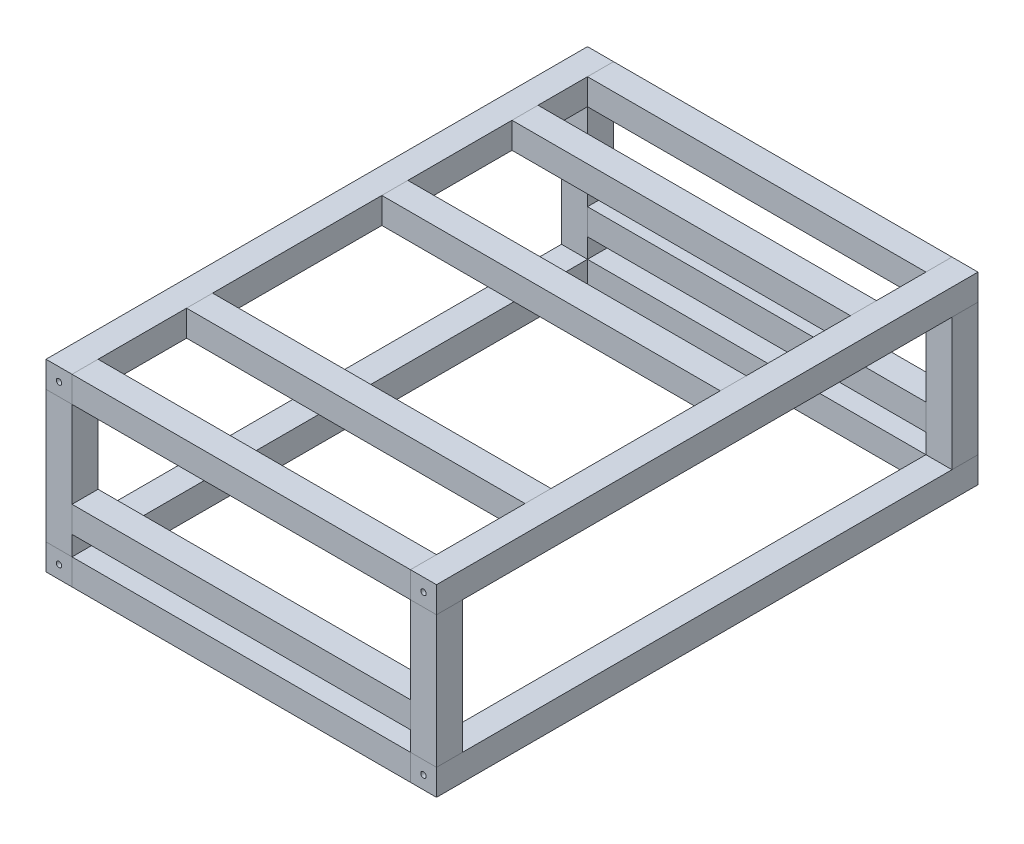
SolidWorks part; units mm, degrees
ref_plane "Front Plane" through (0, 0, 0) normal (0, 0, 1) x (1, 0, 0)
ref_plane "Top Plane" through (0, 0, 0) normal (0, 1, 0) x (1, 0, 0)
ref_plane "Right Plane" through (0, 0, 0) normal (1, 0, 0) x (0, 0, -1)
ref_plane "PL_Xm208" through (0, 0, -208) normal (0, 0, 1) x (1, 0, 0)
sketch "SK_BotSideRails" plane through (0, 0, -208) normal (0, 0, 1) x (1, 0, 0)
  line L1 (130, 36.5) -> (150, 36.5)
  line L2 (130, 36.5) -> (130, 56.5)
  line L3 (130, 56.5) -> (150, 56.5)
  line L4 (150, 36.5) -> (150, 56.5)
  line L6 (-130, 36.5) -> (-150, 36.5)
  line L7 (-130, 36.5) -> (-130, 56.5)
  line L8 (-130, 56.5) -> (-150, 56.5)
  line L9 (-150, 36.5) -> (-150, 56.5)
  circle A0 centre (140, 46.5) radius 2.1
  circle A1 centre (-140, 46.5) radius 2.1
  dimension "D7" = 4.2
  dimension "D14" = 4.2
  dimension "D1" = 20
  dimension "D2" = 20
  dimension "D3" = 130
  dimension "D4" = 36.5
  dimension "D5" = 140
  dimension "D6" = 46.5
  dimension "D8" = 20
  dimension "D9" = 20
  dimension "D10" = 130
  dimension "D11" = 36.5
  dimension "D12" = 140
  dimension "D13" = 46.5
extrude "EX_BotSideRails" add sketch "SK_BotSideRails" along normal blind 416 separate body
sketch "SK_TopSideRails" plane through (0, 0, -208) normal (0, 0, 1) x (1, 0, 0)
  line L1 (130, 158) -> (150, 158)
  line L2 (130, 158) -> (130, 178)
  line L3 (130, 178) -> (150, 178)
  line L4 (150, 158) -> (150, 178)
  line L6 (-130, 158) -> (-150, 158)
  line L7 (-130, 158) -> (-130, 178)
  line L8 (-130, 178) -> (-150, 178)
  line L9 (-150, 158) -> (-150, 178)
  circle A0 centre (140, 168) radius 2.1
  circle A1 centre (-140, 168) radius 2.1
  dimension "D7" = 4.2
  dimension "D14" = 4.2
  dimension "D1" = 20
  dimension "D2" = 20
  dimension "D3" = 130
  dimension "D5" = 140
  dimension "D8" = 20
  dimension "D9" = 20
  dimension "D10" = 130
  dimension "D12" = 140
  dimension "D4" = 158
  dimension "D6" = 168
  dimension "D11" = 158
  dimension "D13" = 168
extrude "EX_TopSideRails" add sketch "SK_TopSideRails" along normal blind 416 separate body
ref_plane "PL_Ym130" through (-130, 0, 0) normal (1, 0, 0) x (0, 0, -1)
sketch "SK_BotEndRails" plane through (-130, 0, 0) normal (1, 0, 0) x (0, 0, -1)
  line L1 (-188, 36.5) -> (-208, 36.5)
  line L2 (-188, 36.5) -> (-188, 56.5)
  line L3 (-188, 56.5) -> (-208, 56.5)
  line L4 (-208, 36.5) -> (-208, 56.5)
  line L6 (188, 36.5) -> (208, 36.5)
  line L7 (188, 36.5) -> (188, 56.5)
  line L8 (188, 56.5) -> (208, 56.5)
  line L9 (208, 36.5) -> (208, 56.5)
  circle A0 centre (-198, 46.5) radius 2.1
  circle A1 centre (198, 46.5) radius 2.1
  dimension "D7" = 4.2
  dimension "D14" = 4.2
  dimension "D1" = 20
  dimension "D2" = 20
  dimension "D4" = 36.5
  dimension "D6" = 46.5
  dimension "D8" = 20
  dimension "D9" = 20
  dimension "D11" = 36.5
  dimension "D13" = 46.5
  dimension "D3" = 188
  dimension "D5" = 198
  dimension "D10" = 188
  dimension "D12" = 198
extrude "EX_BotEndRails" add sketch "SK_BotEndRails" along normal blind 260 separate body
sketch "SK_TopEndRails" plane through (-130, 0, 0) normal (1, 0, 0) x (0, 0, -1)
  line L1 (-188, 158) -> (-208, 158)
  line L2 (-188, 158) -> (-188, 178)
  line L3 (-188, 178) -> (-208, 178)
  line L4 (-208, 158) -> (-208, 178)
  line L6 (188, 158) -> (208, 158)
  line L7 (188, 158) -> (188, 178)
  line L8 (188, 178) -> (208, 178)
  line L9 (208, 158) -> (208, 178)
  circle A0 centre (-198, 168) radius 2.1
  circle A1 centre (198, 168) radius 2.1
  dimension "D7" = 4.2
  dimension "D14" = 4.2
  dimension "D1" = 20
  dimension "D2" = 20
  dimension "D8" = 20
  dimension "D9" = 20
  dimension "D4" = 158
  dimension "D6" = 168
  dimension "D11" = 158
  dimension "D13" = 168
  dimension "D3" = 188
  dimension "D5" = 198
  dimension "D10" = 188
  dimension "D12" = 198
extrude "EX_TopEndRails" add sketch "SK_TopEndRails" along normal blind 260 separate body
sketch "SK_MidCross" plane through (-130, 0, 0) normal (1, 0, 0) x (0, 0, -1)
  line L1 (-188, 71.5) -> (-208, 71.5)
  line L2 (-188, 71.5) -> (-188, 91.5)
  line L3 (-188, 91.5) -> (-208, 91.5)
  line L4 (-208, 71.5) -> (-208, 91.5)
  line L6 (188, 71.5) -> (208, 71.5)
  line L7 (188, 71.5) -> (188, 91.5)
  line L8 (188, 91.5) -> (208, 91.5)
  line L9 (208, 71.5) -> (208, 91.5)
  circle A0 centre (-198, 81.5) radius 2.1
  circle A1 centre (198, 81.5) radius 2.1
  dimension "D7" = 4.2
  dimension "D14" = 4.2
  dimension "D1" = 20
  dimension "D2" = 20
  dimension "D8" = 20
  dimension "D9" = 20
  dimension "D3" = 188
  dimension "D5" = 198
  dimension "D10" = 188
  dimension "D12" = 198
  dimension "D4" = 71.5
  dimension "D6" = 81.5
  dimension "D11" = 71.5
  dimension "D13" = 81.5
extrude "EX_MidCross" add sketch "SK_MidCross" along normal blind 260 separate body
sketch "SK_TopCross" plane through (-130, 0, 0) normal (1, 0, 0) x (0, 0, -1)
  line L1 (30, 158) -> (50, 158)
  line L2 (30, 158) -> (30, 178)
  line L3 (30, 178) -> (50, 178)
  line L4 (50, 158) -> (50, 178)
  line L6 (130, 158) -> (150, 158)
  line L7 (130, 158) -> (130, 178)
  line L8 (130, 178) -> (150, 178)
  line L9 (150, 158) -> (150, 178)
  line L11 (-100, 158) -> (-120, 158)
  line L12 (-100, 158) -> (-100, 178)
  line L13 (-100, 178) -> (-120, 178)
  line L14 (-120, 158) -> (-120, 178)
  circle A0 centre (40, 168) radius 2.1
  circle A1 centre (140, 168) radius 2.1
  circle A2 centre (-110, 168) radius 2.1
  dimension "D14" = 4.2
  dimension "D1" = 20
  dimension "D2" = 20
  dimension "D8" = 20
  dimension "D9" = 20
  dimension "D10" = 130
  dimension "D12" = 140
  dimension "D4" = 158
  dimension "D6" = 168
  dimension "D11" = 158
  dimension "D13" = 168
  dimension "D7" = 4.2
  dimension "D21" = 4.2
  dimension "D3" = 30
  dimension "D5" = 40
  dimension "D15" = 20
  dimension "D16" = 20
  dimension "D17" = 100
  dimension "D18" = 158
  dimension "D19" = 110
  dimension "D20" = 168
extrude "EX_TopCross" add sketch "SK_TopCross" along normal blind 260 separate body
ref_plane "PL_Zp56_5" through (0, 56.5, 0) normal (0, 1, 0) x (1, 0, 0)
sketch "SK_Uprights" plane through (0, 56.5, 0) normal (0, 1, 0) x (1, 0, 0)
  line L1 (130, -188) -> (150, -188)
  line L2 (130, -188) -> (130, -208)
  line L3 (130, -208) -> (150, -208)
  line L4 (150, -188) -> (150, -208)
  line L6 (-130, -188) -> (-150, -188)
  line L7 (-130, -188) -> (-130, -208)
  line L8 (-130, -208) -> (-150, -208)
  line L9 (-150, -188) -> (-150, -208)
  line L11 (130, 188) -> (150, 188)
  line L12 (130, 188) -> (130, 208)
  line L13 (130, 208) -> (150, 208)
  line L14 (150, 188) -> (150, 208)
  line L16 (-130, 188) -> (-150, 188)
  line L17 (-130, 188) -> (-130, 208)
  line L18 (-130, 208) -> (-150, 208)
  line L19 (-150, 188) -> (-150, 208)
  circle A0 centre (140, -198) radius 2.1
  circle A1 centre (-140, -198) radius 2.1
  circle A2 centre (140, 198) radius 2.1
  circle A3 centre (-140, 198) radius 2.1
  dimension "D7" = 4.2
  dimension "D14" = 4.2
  dimension "D1" = 20
  dimension "D2" = 20
  dimension "D8" = 20
  dimension "D9" = 20
  dimension "D3" = 188
  dimension "D5" = 198
  dimension "D10" = 188
  dimension "D12" = 198
  dimension "D15" = 20
  dimension "D16" = 20
  dimension "D21" = 4.2
  dimension "D28" = 4.2
  dimension "D4" = 130
  dimension "D6" = 140
  dimension "D11" = 130
  dimension "D13" = 140
  dimension "D17" = 188
  dimension "D18" = 130
  dimension "D19" = 198
  dimension "D20" = 140
  dimension "D22" = 20
  dimension "D23" = 20
  dimension "D24" = 188
  dimension "D25" = 130
  dimension "D26" = 198
  dimension "D27" = 140
extrude "EX_Uprights" add sketch "SK_Uprights" along normal blind 101.5 separate body
ref_axis "AX_X" through (0, 0, -228.8) along (0, 0, 1)
ref_axis "AX_Y" through (165, 0, 0) along (-1, 0, 0)
ref_axis "AX_Z" through (0, 185.075, 0) along (0, -1, 0)
equation "\"BODY_L\"= 420"
equation "\"BODY_W\"= 340"
equation "\"FLOOR_Z\"= 35"
equation "\"DECK_Z\"= 180"
equation "\"DECK_T\"= 2"
equation "\"GRID\"= 20"
equation "\"PROFILE\"= 20"
equation "\"SM_T\"= 1.5"
equation "\"PAN_T\"= 1.5"
equation "\"PAN_TOP\"= \"FLOOR_Z\" + \"PAN_T\""
equation "\"RAIL_Y\"= 140"
equation "\"RAIL_X\"= \"BODY_L\" / 2 - \"PROFILE\" / 2 - 2"
equation "\"BOTRING_Z\"= \"PAN_TOP\" + \"PROFILE\" / 2"
equation "\"TOPRING_Z\"= \"DECK_Z\" - \"DECK_T\" - \"PROFILE\" / 2"
equation "\"DRAWER_Z\"= 93"
equation "\"MIDX_Z\"= \"DRAWER_Z\" - \"SM_T\" - \"PROFILE\" / 2"
equation "\"SKIN_Y\"= \"RAIL_Y\" + \"PROFILE\" / 2"
equation "\"SKIN_T\"= 2"
equation "\"WHEEL_D\"= 144"
equation "\"WHEEL_W\"= 52"
equation "\"TRACK\"= 365"
equation "\"AXLE_Z\"= \"WHEEL_D\" / 2"
equation "\"WHEEL_WEB_OFF\"= 6"
equation "\"HUB_T\"= 8"
equation "\"BUSHING_L\"= 6"
equation "\"HUB_GAP\"= 1"
equation "\"MOTOR_UP\"= 7"
equation "\"MOTOR_FACE_Y\"= \"TRACK\" / 2 + \"WHEEL_WEB_OFF\" - (\"BUSHING_L\" + \"HUB_GAP\" + \"HUB_T\")"
equation "\"MOTOR_AXIS_Z\"= \"AXLE_Z\" + \"MOTOR_UP\""
equation "\"CASTER_D\"= 50"
equation "\"CASTER_X\"= 150"
equation "\"CASTER_H\"= 68"
equation "\"POST_X\"= -40"
equation "\"POST_DY\"= 120"
equation "\"POST_SIZE\"= 20"
equation "\"POST_TOP\"= 400"
equation "\"BRACE_Z\"= 335"
equation "\"STRUT_X0\"= -140"
equation "\"HEAD_X0\"= -110"
equation "\"HEAD_X1\"= 12"
equation "\"BEZEL_T\"= 3"
equation "\"WEDGE_MID\"= 7.7"
equation "\"OAK_D\"= 22.9"
equation "\"HEAD_W\"= 210"
equation "\"HEAD_Z0\"= \"POST_TOP\""
equation "\"HEAD_TOP\"= 525"
equation "\"HEAD_TOP_X\"= -20"
equation "\"SCREEN_ANG\"= 35"
equation "\"LENS_X\"= 45.6"
equation "\"LENS_Z\"= 450"
equation "\"OAK_TILT\"= 5"
equation "\"OAK_VFOV_DEPTH\"= 79.5"
equation "\"OAK_VFOV_RGB\"= 72"
equation "\"LIDAR_X\"= 110"
equation "\"SCAN_Z\"= 260"
equation "\"STRUT_Z\"= \"SCAN_Z\" - 20"
equation "\"LIDAR_SCAN_H\"= 27.2"
equation "\"LIDAR_MOUNT_Z\"= \"SCAN_Z\" - \"LIDAR_SCAN_H\""
equation "\"ESTOP_X\"= -172.5"
equation "\"ESTOP_Y\"= -127.5"
equation "\"ESTOP_TOP\"= 225"
equation "\"BUMPER_T\"= 15"
equation "\"BUMPER_Z0\"= 40"
equation "\"BUMPER_Z1\"= 130"
equation "\"CLIFF_X\"= 218"
equation "\"CLIFF_Y\"= 105"
equation "\"CLIFF_Z\"= 72"
equation "\"CLIFF_ANG\"= 50"
equation "\"CONTACT_X\"= 216"
equation "\"CONTACT_Y\"= 64"
equation "\"CONTACT_Z\"= 30"
equation "\"DOCK_TAG_DIST\"= 250"
equation "\"DOCK_TAG_SIZE\"= 80"
equation "\"DOCK_TAG_Z\"= 400"
equation "\"BAT_L\"= 240"
equation "\"BAT_W\"= 90"
equation "\"BAT_H\"= 58"
equation "\"BAT_Z\"= \"DRAWER_Z\" + \"SM_T\""
equation "\"BAT_X\"= 0"
equation "\"PCB_L\"= 95"
equation "\"PCB_W\"= 120"
equation "\"PCB_H\"= 40"
equation "\"PCB_X\"= 62.5"
equation "\"DRV_X\"= 85"
equation "\"DRV_Y\"= 100"
equation "\"DRV_S\"= 50"
equation "\"COMPUTE_X\"= -65"
equation "\"COMPUTE_L\"= 90"
equation "\"COMPUTE_W\"= 160"
equation "\"D1@PL_Xm208\" = \"RAIL_X\" + \"PROFILE\" / 2"
equation "\"D1@SK_BotSideRails\" = \"PROFILE\""
equation "\"D2@SK_BotSideRails\" = \"PROFILE\""
equation "\"D3@SK_BotSideRails\" = abs(\"RAIL_Y\") - \"PROFILE\" / 2"
equation "\"D4@SK_BotSideRails\" = abs(\"BOTRING_Z\") - \"PROFILE\" / 2"
equation "\"D5@SK_BotSideRails\" = abs(\"RAIL_Y\")"
equation "\"D6@SK_BotSideRails\" = abs(\"BOTRING_Z\")"
equation "\"D8@SK_BotSideRails\" = \"PROFILE\""
equation "\"D9@SK_BotSideRails\" = \"PROFILE\""
equation "\"D10@SK_BotSideRails\" = abs(\"RAIL_Y\") - \"PROFILE\" / 2"
equation "\"D11@SK_BotSideRails\" = abs(\"BOTRING_Z\") - \"PROFILE\" / 2"
equation "\"D12@SK_BotSideRails\" = abs(\"RAIL_Y\")"
equation "\"D13@SK_BotSideRails\" = abs(\"BOTRING_Z\")"
equation "\"D1@EX_BotSideRails\" = 2 * \"RAIL_X\" + \"PROFILE\""
equation "\"D1@SK_TopSideRails\" = \"PROFILE\""
equation "\"D2@SK_TopSideRails\" = \"PROFILE\""
equation "\"D3@SK_TopSideRails\" = abs(\"RAIL_Y\") - \"PROFILE\" / 2"
equation "\"D4@SK_TopSideRails\" = abs(\"TOPRING_Z\") - \"PROFILE\" / 2"
equation "\"D5@SK_TopSideRails\" = abs(\"RAIL_Y\")"
equation "\"D6@SK_TopSideRails\" = abs(\"TOPRING_Z\")"
equation "\"D8@SK_TopSideRails\" = \"PROFILE\""
equation "\"D9@SK_TopSideRails\" = \"PROFILE\""
equation "\"D10@SK_TopSideRails\" = abs(\"RAIL_Y\") - \"PROFILE\" / 2"
equation "\"D11@SK_TopSideRails\" = abs(\"TOPRING_Z\") - \"PROFILE\" / 2"
equation "\"D12@SK_TopSideRails\" = abs(\"RAIL_Y\")"
equation "\"D13@SK_TopSideRails\" = abs(\"TOPRING_Z\")"
equation "\"D1@EX_TopSideRails\" = 2 * \"RAIL_X\" + \"PROFILE\""
equation "\"D1@PL_Ym130\" = \"RAIL_Y\" - \"PROFILE\" / 2"
equation "\"D1@SK_BotEndRails\" = \"PROFILE\""
equation "\"D2@SK_BotEndRails\" = \"PROFILE\""
equation "\"D3@SK_BotEndRails\" = abs(\"RAIL_X\") - \"PROFILE\" / 2"
equation "\"D4@SK_BotEndRails\" = abs(\"BOTRING_Z\") - \"PROFILE\" / 2"
equation "\"D5@SK_BotEndRails\" = abs(\"RAIL_X\")"
equation "\"D6@SK_BotEndRails\" = abs(\"BOTRING_Z\")"
equation "\"D8@SK_BotEndRails\" = \"PROFILE\""
equation "\"D9@SK_BotEndRails\" = \"PROFILE\""
equation "\"D10@SK_BotEndRails\" = abs(\"RAIL_X\") - \"PROFILE\" / 2"
equation "\"D11@SK_BotEndRails\" = abs(\"BOTRING_Z\") - \"PROFILE\" / 2"
equation "\"D12@SK_BotEndRails\" = abs(\"RAIL_X\")"
equation "\"D13@SK_BotEndRails\" = abs(\"BOTRING_Z\")"
equation "\"D1@EX_BotEndRails\" = 2 * (\"RAIL_Y\" - \"PROFILE\" / 2)"
equation "\"D1@SK_TopEndRails\" = \"PROFILE\""
equation "\"D2@SK_TopEndRails\" = \"PROFILE\""
equation "\"D3@SK_TopEndRails\" = abs(\"RAIL_X\") - \"PROFILE\" / 2"
equation "\"D4@SK_TopEndRails\" = abs(\"TOPRING_Z\") - \"PROFILE\" / 2"
equation "\"D5@SK_TopEndRails\" = abs(\"RAIL_X\")"
equation "\"D6@SK_TopEndRails\" = abs(\"TOPRING_Z\")"
equation "\"D8@SK_TopEndRails\" = \"PROFILE\""
equation "\"D9@SK_TopEndRails\" = \"PROFILE\""
equation "\"D10@SK_TopEndRails\" = abs(\"RAIL_X\") - \"PROFILE\" / 2"
equation "\"D11@SK_TopEndRails\" = abs(\"TOPRING_Z\") - \"PROFILE\" / 2"
equation "\"D12@SK_TopEndRails\" = abs(\"RAIL_X\")"
equation "\"D13@SK_TopEndRails\" = abs(\"TOPRING_Z\")"
equation "\"D1@EX_TopEndRails\" = 2 * (\"RAIL_Y\" - \"PROFILE\" / 2)"
equation "\"D1@SK_MidCross\" = \"PROFILE\""
equation "\"D2@SK_MidCross\" = \"PROFILE\""
equation "\"D3@SK_MidCross\" = abs(\"RAIL_X\") - \"PROFILE\" / 2"
equation "\"D4@SK_MidCross\" = abs(\"MIDX_Z\") - \"PROFILE\" / 2"
equation "\"D5@SK_MidCross\" = abs(\"RAIL_X\")"
equation "\"D6@SK_MidCross\" = abs(\"MIDX_Z\")"
equation "\"D8@SK_MidCross\" = \"PROFILE\""
equation "\"D9@SK_MidCross\" = \"PROFILE\""
equation "\"D10@SK_MidCross\" = abs(\"RAIL_X\") - \"PROFILE\" / 2"
equation "\"D11@SK_MidCross\" = abs(\"MIDX_Z\") - \"PROFILE\" / 2"
equation "\"D12@SK_MidCross\" = abs(\"RAIL_X\")"
equation "\"D13@SK_MidCross\" = abs(\"MIDX_Z\")"
equation "\"D1@EX_MidCross\" = 2 * (\"RAIL_Y\" - \"PROFILE\" / 2)"
equation "\"D1@SK_TopCross\" = \"PROFILE\""
equation "\"D2@SK_TopCross\" = \"PROFILE\""
equation "\"D3@SK_TopCross\" = abs(\"POST_X\") - \"PROFILE\" / 2"
equation "\"D4@SK_TopCross\" = abs(\"TOPRING_Z\") - \"PROFILE\" / 2"
equation "\"D5@SK_TopCross\" = abs(\"POST_X\")"
equation "\"D6@SK_TopCross\" = abs(\"TOPRING_Z\")"
equation "\"D8@SK_TopCross\" = \"PROFILE\""
equation "\"D9@SK_TopCross\" = \"PROFILE\""
equation "\"D10@SK_TopCross\" = abs(\"STRUT_X0\") - \"PROFILE\" / 2"
equation "\"D11@SK_TopCross\" = abs(\"TOPRING_Z\") - \"PROFILE\" / 2"
equation "\"D12@SK_TopCross\" = abs(\"STRUT_X0\")"
equation "\"D13@SK_TopCross\" = abs(\"TOPRING_Z\")"
equation "\"D15@SK_TopCross\" = \"PROFILE\""
equation "\"D16@SK_TopCross\" = \"PROFILE\""
equation "\"D17@SK_TopCross\" = abs(\"LIDAR_X\") - \"PROFILE\" / 2"
equation "\"D18@SK_TopCross\" = abs(\"TOPRING_Z\") - \"PROFILE\" / 2"
equation "\"D19@SK_TopCross\" = abs(\"LIDAR_X\")"
equation "\"D20@SK_TopCross\" = abs(\"TOPRING_Z\")"
equation "\"D1@EX_TopCross\" = 2 * (\"RAIL_Y\" - \"PROFILE\" / 2)"
equation "\"D1@PL_Zp56_5\" = \"BOTRING_Z\" + \"PROFILE\" / 2"
equation "\"D1@SK_Uprights\" = \"PROFILE\""
equation "\"D2@SK_Uprights\" = \"PROFILE\""
equation "\"D3@SK_Uprights\" = abs(\"RAIL_X\") - \"PROFILE\" / 2"
equation "\"D4@SK_Uprights\" = abs(\"RAIL_Y\") - \"PROFILE\" / 2"
equation "\"D5@SK_Uprights\" = abs(\"RAIL_X\")"
equation "\"D6@SK_Uprights\" = abs(\"RAIL_Y\")"
equation "\"D8@SK_Uprights\" = \"PROFILE\""
equation "\"D9@SK_Uprights\" = \"PROFILE\""
equation "\"D10@SK_Uprights\" = abs(\"RAIL_X\") - \"PROFILE\" / 2"
equation "\"D11@SK_Uprights\" = abs(\"RAIL_Y\") - \"PROFILE\" / 2"
equation "\"D12@SK_Uprights\" = abs(\"RAIL_X\")"
equation "\"D13@SK_Uprights\" = abs(\"RAIL_Y\")"
equation "\"D15@SK_Uprights\" = \"PROFILE\""
equation "\"D16@SK_Uprights\" = \"PROFILE\""
equation "\"D17@SK_Uprights\" = abs(\"RAIL_X\") - \"PROFILE\" / 2"
equation "\"D18@SK_Uprights\" = abs(\"RAIL_Y\") - \"PROFILE\" / 2"
equation "\"D19@SK_Uprights\" = abs(\"RAIL_X\")"
equation "\"D20@SK_Uprights\" = abs(\"RAIL_Y\")"
equation "\"D22@SK_Uprights\" = \"PROFILE\""
equation "\"D23@SK_Uprights\" = \"PROFILE\""
equation "\"D24@SK_Uprights\" = abs(\"RAIL_X\") - \"PROFILE\" / 2"
equation "\"D25@SK_Uprights\" = abs(\"RAIL_Y\") - \"PROFILE\" / 2"
equation "\"D26@SK_Uprights\" = abs(\"RAIL_X\")"
equation "\"D27@SK_Uprights\" = abs(\"RAIL_Y\")"
equation "\"D1@EX_Uprights\" = \"TOPRING_Z\" - \"BOTRING_Z\" - \"PROFILE\""
